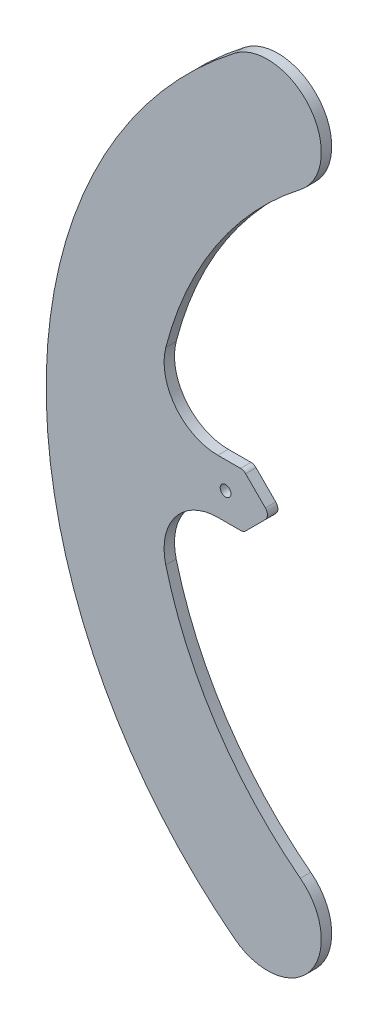
SolidWorks part; units mm, degrees
ref_plane "Front Plane" through (0, 0, 0) normal (0, 0, 1) x (1, 0, 0)
ref_plane "Top Plane" through (0, 0, 0) normal (0, 1, 0) x (1, 0, 0)
ref_plane "Right Plane" through (0, 0, 0) normal (1, 0, 0) x (0, 0, -1)
sketch "Sketch1" plane through (0, 0, 0) normal (0, 0, 1) x (1, 0, 0)
  line L0 (-32.8019, 0) -> (18.2589, 0) construction
  line L1 (70.5, 105) -> (70.5, 135) construction
  line L2 (205.5, -110) -> (-64.5, -110)
  line L3 (205.5, -110) -> (205.5, 110)
  line L4 (205.5, 110) -> (-64.5, 110)
  line L5 (-19.5, 6.5) -> (-19.5, -6.5)
  line L6 (-18.5, -7.5) -> (-9.5, -7.5)
  line L7 (-9.5, -7.5) -> (-2, 0)
  line L9 (-9.5, 7.5) -> (-18.5, 7.5)
  line L11 (-18.5, -7.5) -> (-9.5, -7.5)
  line L15 (-64.5, -110) -> (-64.5, 110)
  line L16 (205.5, -110) -> (-64.5, 110) construction
  line L17 (205.5, 110) -> (-64.5, -110) construction
  line L18 (-18, 7.5) -> (-34.2318, 7.5)
  line L19 (-18.5, -7.5) -> (-34.2318, -7.5)
  line L146 (-9.5, 7.5) -> (-18.5, 7.5)
  line L162 (-9.5, -7.5) -> (-2, 0)
  line L169 (-2, 0) -> (-9.5, 7.5)
  line L170 (-2, 0) -> (-9.5, 7.5)
  line L176 (-19.5, 6.5) -> (-19.5, -6.5)
  circle A0 centre (-14.5, 0) radius 1.5 construction
  arc A2 (-19.5, -6.5) -> (-18.5, -7.5) centre (-18.5, -6.5) ccw
  circle A6 centre (-14.5, 0) radius 1.5
  circle A7 centre (-14.5, 0) radius 1.5
  circle A8 centre (70.5, 0) radius 135
  circle A9 centre (70.5, 0) radius 105
  circle A11 centre (-2.8144, 95) radius 15
  circle A12 centre (-2.8144, -95) radius 15
  arc A65 (-19.5, -6.5) -> (-18.5, -7.5) centre (-18.5, -6.5) ccw
  arc A77 (-18.5, 7.5) -> (-19.5, 6.5) centre (-18.5, 6.5) ccw
  arc A78 (-18.5, 7.5) -> (-19.5, 6.5) centre (-18.5, 6.5) ccw
  point P19 (-64.5, 0)
  point P27 (70.5, 110)
  dimension "D3" = 270
  dimension "D5" = 30
  dimension "D2" = 55
  dimension "D4" = 220
  dimension "D1" = 0
extrude "Boss-Extrude1" add sketch "Sketch1" along normal blind 2.9 contours A11 | A8 A12 A9 A11 | A12 | L18 A9 L19 | L146 L11 L162 L170 A6 region at (-2.8144, -95, 0) region at (-37.1858, 0, 0) region at (-2.8144, 95, 0) region at (-26.9408, 0, 0) region at (-12.3671, 0, 0)
fillet "Fillet1" radius 15 2 edges at (-34.2318, -7.5, 1.45) (-34.2318, 7.5, 1.45)
fillet "Fillet2" radius 2 3 edges at (-9.5, -7.5, 1.45) (-9.5, 7.5, 1.45) (-2, 0, 1.45)
